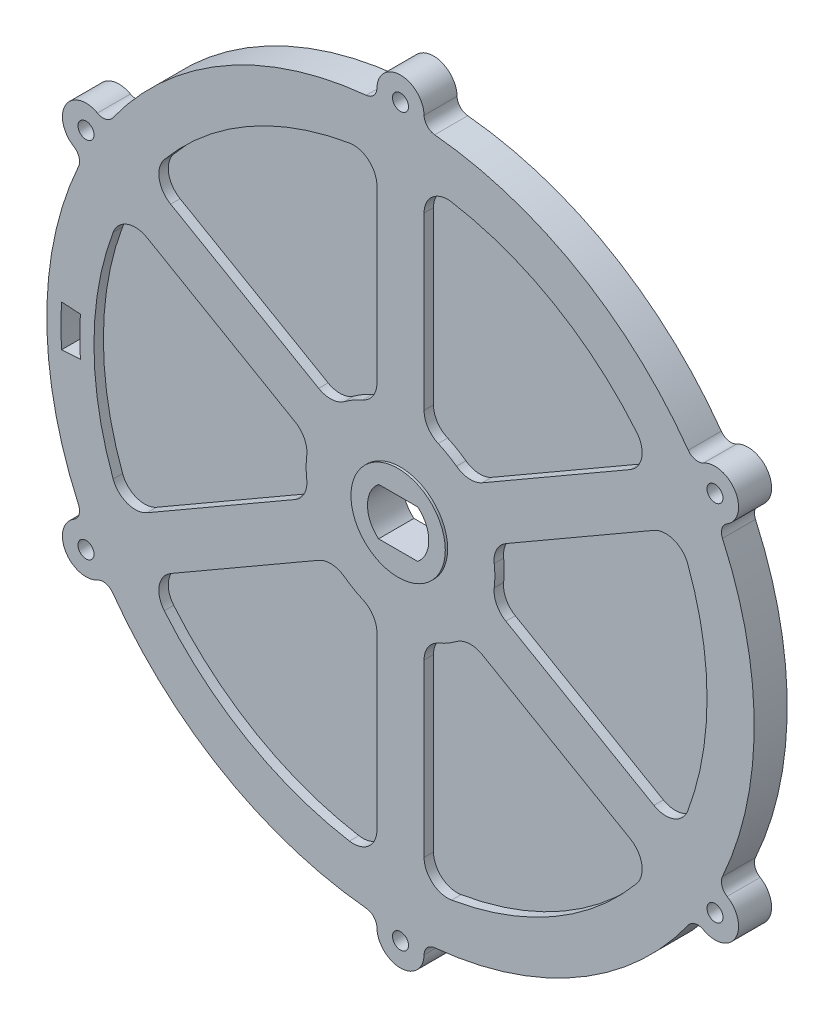
SolidWorks part; units mm, degrees
ref_plane "Front Plane" through (0, 0, 0) normal (0, 0, 1) x (1, 0, 0)
ref_plane "Top Plane" through (0, 0, 0) normal (0, 1, 0) x (1, 0, 0)
ref_plane "Right Plane" through (0, 0, 0) normal (1, 0, 0) x (0, 0, -1)
sketch "Sketch2" plane through (0, 0, 0) normal (0, 0, 1) x (1, 0, 0)
  line L0 (4.1533, 5) -> (-4.1533, 5)
  line L1 (4.1533, -5) -> (-4.1533, -5)
  circle A0 centre (0, 0) radius 75
  circle A1 centre (0, 0) radius 6.5
  point P8 (5.0022, -3.8494)
  point P9 (0, 0)
  point P10 (0, 0)
  point P11 (2.1037, -6.1502)
  point P12 (5.5221, 3.4287)
  point P13 (0, 0)
  point P14 (0, 0)
  point P15 (0.8969, -6.4378)
  point P16 (2.9707, -5.7814)
  point P17 (-5.119, 4.0057)
  point P18 (0, 0)
  point P19 (-0.8621, 6.4426)
  point P20 (-1.0534, -6.4141)
  point P21 (2.3696, 6.0527)
  point P22 (-3.4323, -5.5199)
  point P23 (3.5016, 5.4762)
  point P24 (4.8717, 4.3031)
  dimension "D1" = 150
  dimension "D2" = 13
  dimension "D3" = 10
extrude "Boss-Extrude1" add sketch "Sketch2" along normal mid plane 7 contours A0 A1 | L0 A1 | L1 A1 region at (0, 5.6064, 0) region at (0, -5.6064, 0) region at (-72.8787, 0, 0)
sketch "Sketch3" plane through (0, 0, 3.5) normal (0, 0, 1) x (1, 0, 0)
  circle A0 centre (0, 0) radius 10
  arc M2 (4.1533, 5) -> (4.1533, -5) centre (0, 0) cw
  line M3 (4.1533, -5) -> (-4.1533, -5)
  arc M4 (-4.1533, -5) -> (-4.1533, 5) centre (0, 0) cw
  line M5 (-4.1533, 5) -> (4.1533, 5)
  dimension "D1" = 20
extrude "Boss-Extrude2" add sketch "Sketch3" along normal blind 0.5 contours A0 M5 M2 M3 M4 region at (-9.7172, 0, 3.5)
sketch "Sketch4" plane through (0, 0, -3.5) normal (0, 0, 1) x (1, 0, 0)
  line L0 (5, 77) -> (5, 74.8331)
  line L1 (-5, 77) -> (-5, 74.8331)
  arc A0 (5, 77) -> (-5, 77) centre (0, 77) ccw
  circle A1 centre (0, 0) radius 75 construction
  circle A3 centre (0, 0) radius 75
  arc A4 (-5, 74.8331) -> (5, 74.8331) centre (0, 0) ccw
  circle M9 centre (0, 0) radius 75
  dimension "D1" = 5
  dimension "D2" = 77
  dimension "D3" = 0
extrude "Boss-Extrude3" add sketch "Sketch4" along normal up to surface (7 mm away) contours A0 L0 L1 M9 region at (0, 78.0396, -3.5) up to face at (10, 0, 3.5)
fillet "Fillet1" radius 2.5 2 edges at (-5, 74.8331, 0) (5, 74.8331, 0)
sketch "Sketch6" plane through (0, 0, -3.5) normal (0, 0, -1) x (-1, 0, 0)
  circle A0 centre (0, 77) radius 1.7
  arc A4 (4.9992, 77.0909) -> (-4.9992, 77.0909) centre (0, 77) ccw construction
  dimension "D1" = 3.4
extrude "Cut-Extrude1" cut sketch "Sketch6" against normal through all
pattern_circular "CirPattern1" count 6 over 360 about axis through (0, 0, -3.5) along (0, 0, 1) of "Boss-Extrude3", "Cut-Extrude1", "Fillet1"
sketch "Sketch7" plane through (0, 0, -3.5) normal (0, 0, -1) x (-1, 0, 0)
  line L0 (-5, 59.1608) -> (-5, 22.9129)
  line L1 (5, 59.1608) -> (5, 22.9129)
  line L2 (-5, 19.3649) -> (5, 19.3649) construction
  line L3 (48.7348, 33.9105) -> (17.3431, 15.7866)
  line L4 (53.7348, 25.2503) -> (22.3431, 7.1263)
  line L6 (53.7348, -25.2503) -> (22.3431, -7.1263)
  line L7 (48.7348, -33.9105) -> (17.3431, -15.7866)
  line L9 (5, -59.1608) -> (5, -22.9129)
  line L10 (-5, -59.1608) -> (-5, -22.9129)
  line L12 (-48.7348, -33.9105) -> (-17.3431, -15.7866)
  line L13 (-53.7348, -25.2503) -> (-22.3431, -7.1263)
  line L15 (-53.7348, 25.2503) -> (-22.3431, 7.1263)
  line L16 (-48.7348, 33.9105) -> (-17.3431, 15.7866)
  line L18 (0, 0) -> (8, 18.3303) construction
  line L19 (14.2705, 14.0126) -> (19.2705, 5.3523) construction
  line L20 (19.2705, -5.3523) -> (14.2705, -14.0126) construction
  line L21 (5, -19.3649) -> (-5, -19.3649) construction
  line L22 (-14.2705, -14.0126) -> (-19.2705, -5.3523) construction
  line L23 (-19.2705, 5.3523) -> (-14.2705, 14.0126) construction
  arc A0 (-8, 18.3303) -> (-11.8745, 16.0934) centre (0, 0) ccw
  arc A1 (-10.8333, 64.0909) -> (-50.0876, 41.4274) centre (0, 0) ccw
  arc A2 (5, 22.9129) -> (8, 18.3303) centre (10, 22.9129) ccw
  arc A3 (5, 59.1608) -> (10.8333, 64.0909) centre (10, 59.1608) cw
  arc A4 (-5, 59.1608) -> (-10.8333, 64.0909) centre (-10, 59.1608) ccw
  arc A5 (-5, 22.9129) -> (-8, 18.3303) centre (-10, 22.9129) cw
  arc A6 (22.3431, 7.1263) -> (19.8745, 2.2369) centre (24.8431, 2.7962) ccw
  arc A7 (53.7348, 25.2503) -> (60.921, 22.6635) centre (56.2348, 20.9201) cw
  arc A8 (48.7348, 33.9105) -> (50.0876, 41.4274) centre (46.2348, 38.2407) ccw
  arc A9 (17.3431, 15.7866) -> (11.8745, 16.0934) centre (14.8431, 20.1167) cw
  arc A10 (17.3431, -15.7866) -> (11.8745, -16.0934) centre (14.8431, -20.1167) ccw
  arc A11 (48.7348, -33.9105) -> (50.0876, -41.4274) centre (46.2348, -38.2407) cw
  arc A12 (53.7348, -25.2503) -> (60.921, -22.6635) centre (56.2348, -20.9201) ccw
  arc A13 (22.3431, -7.1263) -> (19.8745, -2.2369) centre (24.8431, -2.7962) cw
  arc A14 (-5, -22.9129) -> (-8, -18.3303) centre (-10, -22.9129) ccw
  arc A15 (-5, -59.1608) -> (-10.8333, -64.0909) centre (-10, -59.1608) cw
  arc A16 (5, -59.1608) -> (10.8333, -64.0909) centre (10, -59.1608) ccw
  arc A17 (5, -22.9129) -> (8, -18.3303) centre (10, -22.9129) cw
  arc A18 (-22.3431, -7.1263) -> (-19.8745, -2.2369) centre (-24.8431, -2.7962) ccw
  arc A19 (-53.7348, -25.2503) -> (-60.921, -22.6635) centre (-56.2348, -20.9201) cw
  arc A20 (-48.7348, -33.9105) -> (-50.0876, -41.4274) centre (-46.2348, -38.2407) ccw
  arc A21 (-17.3431, -15.7866) -> (-11.8745, -16.0934) centre (-14.8431, -20.1167) cw
  arc A22 (-17.3431, 15.7866) -> (-11.8745, 16.0934) centre (-14.8431, 20.1167) ccw
  arc A23 (-48.7348, 33.9105) -> (-50.0876, 41.4274) centre (-46.2348, 38.2407) cw
  arc A24 (-53.7348, 25.2503) -> (-60.921, 22.6635) centre (-56.2348, 20.9201) ccw
  arc A25 (-22.3431, 7.1263) -> (-19.8745, 2.2369) centre (-24.8431, 2.7962) cw
  arc A26 (11.8745, 16.0934) -> (8, 18.3303) centre (0, 0) ccw
  arc A27 (19.8745, -2.2369) -> (19.8745, 2.2369) centre (0, 0) ccw
  arc A28 (8, -18.3303) -> (11.8745, -16.0934) centre (0, 0) ccw
  arc A29 (-11.8745, -16.0934) -> (-8, -18.3303) centre (0, 0) ccw
  arc A30 (-19.8745, 2.2369) -> (-19.8745, -2.2369) centre (0, 0) ccw
  arc A31 (50.0876, 41.4274) -> (10.8333, 64.0909) centre (0, 0) ccw
  arc A32 (60.921, -22.6635) -> (60.921, 22.6635) centre (0, 0) ccw
  arc A33 (10.8333, -64.0909) -> (50.0876, -41.4274) centre (0, 0) ccw
  arc A34 (-50.0876, -41.4274) -> (-10.8333, -64.0909) centre (0, 0) ccw
  arc A35 (-60.921, 22.6635) -> (-60.921, -22.6635) centre (0, 0) ccw
  point P8 (0, 19.3649)
  dimension "D1" = 130
  dimension "D2" = 40
  dimension "D4" = 5
  dimension "D3" = 10
  dimension "D5" = 6
extrude "Cut-Extrude2" cut sketch "Sketch7" against normal blind 2
mirror "Mirror1" about plane through (0, 0, 0) normal (0, 0, 1) of "Cut-Extrude2"
sketch "Sketch9" plane through (0, 0, 0) normal (0, 1, 0) x (1, 0, 0)
  line L0 (-7.2569, 3.5) -> (-61.0187, 3.5) construction
  line L1 (-72, -3.5) -> (-68, -3.5)
  line L2 (-72, -3.5) -> (-72, 3.5)
  line L3 (-72, 3.5) -> (-68, 3.5)
  line L4 (-68, -3.5) -> (-68, 3.5)
  line L5 (-61.0187, -3.5) -> (-7.2569, -3.5) construction
  line L6 (0, 0) -> (0, 49.8627) construction
  dimension "D1" = 4
  dimension "D2" = 72
revolve "Cut-Revolve1" cut sketch "Sketch9" angle 7 mid plane about L6
